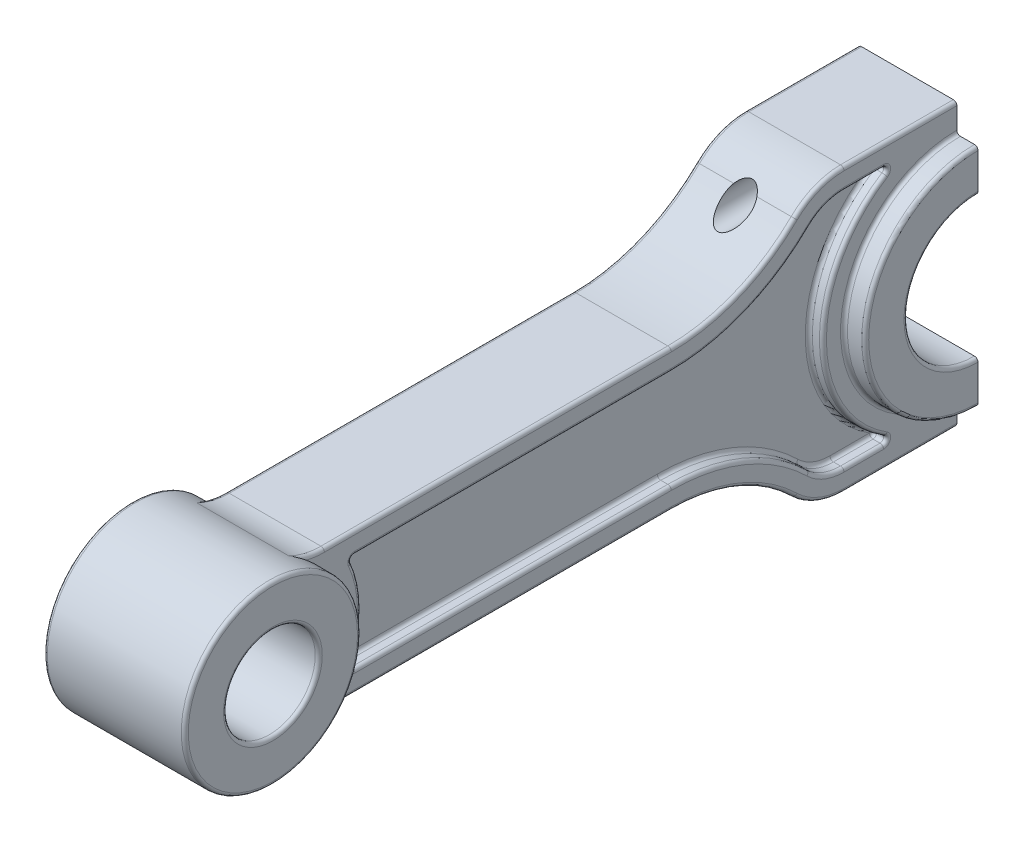
SolidWorks part; units mm, degrees
material "AISI 4340 Steel, normalized"
ref_plane "Front Plane" through (0, 0, 0) normal (1, 0, 0) x (0, 1, 0)
ref_plane "Top Plane" through (0, 0, 0) normal (0, 0, 1) x (0, 1, 0)
ref_plane "Right Plane" through (0, 0, 0) normal (0, 1, 0) x (-1, 0, 0)
sketch "Sketch1" plane through (0, 0, 0) normal (1, 0, 0) x (0, 1, 0)
  line L0 (-21.64, 0) -> (23.8326, 0) construction
  line L1 (-20, 16) -> (-20, 0)
  line L2 (0, 100) -> (0, -41.6338) construction
  line L3 (-10, 40.4949) -> (-10, 92.5)
  line L4 (-20, 0) -> (-10, 0)
  line L5 (10, 0) -> (20, 0)
  line L6 (-17, 16) -> (-17, 10.3923)
  line L7 (-7, 40.4949) -> (-7, 85.3798)
  line L8 (0, 19) -> (-26.4574, 19) construction
  line L9 (-17, 16) -> (-17, 0) construction
  line L10 (-7, 40.4949) -> (-7, 92.5) construction
  line L11 (17, 16) -> (17, 10.3923)
  line L12 (7, 40.4949) -> (7, 85.3798)
  line L13 (20, 16) -> (20, 0)
  line L14 (10, 40.4949) -> (10, 92.5)
  arc A0 (10, 0) -> (-10, 0) centre (0, 0) ccw
  arc A1 (16, 0) -> (-16, 0) centre (0, 0) ccw
  arc A2 (16.0769, 10.1258) -> (-16.0769, 10.1258) centre (0, 0) ccw
  arc A3 (-20, 16) -> (-17.1429, 22.9985) centre (-10, 16) cw
  arc A4 (-17.1429, 22.9985) -> (-10, 40.4949) centre (-35, 40.4949) ccw
  circle A5 centre (0, 100) radius 12.5
  circle A6 centre (0, 100) radius 6.5
  arc A7 (-11.1111, 94.2735) -> (-10, 89.6922) centre (-20, 89.6922) cw
  arc A8 (-17, 16) -> (-15, 20.899) centre (-10, 16) cw
  circle A9 centre (0, 0) radius 19 construction
  circle A10 centre (0, 0) radius 16 construction
  circle A11 centre (0, 0) radius 10 construction
  arc A12 (-15, 20.899) -> (-7, 40.4949) centre (-35, 40.4949) ccw
  arc A13 (-6.2969, 85.8367) -> (6.2969, 85.8367) centre (0, 100) ccw
  arc A14 (17, 16) -> (15, 20.899) centre (10, 16) ccw
  circle A15 centre (0, 100) radius 15.5 construction
  arc A16 (15, 20.899) -> (7, 40.4949) centre (35, 40.4949) cw
  arc A17 (20, 16) -> (17.1429, 22.9985) centre (10, 16) ccw
  arc A18 (17.1429, 22.9985) -> (10, 40.4949) centre (35, 40.4949) cw
  arc A19 (11.1111, 94.2735) -> (10, 89.6922) centre (20, 89.6922) ccw
  arc A20 (7, 85.3798) -> (6.2969, 85.8367) centre (6.5, 85.3798) ccw
  arc A21 (-7, 85.3798) -> (-6.2969, 85.8367) centre (-6.5, 85.3798) cw
  arc A22 (17, 10.3923) -> (16.0769, 10.1258) centre (16.5, 10.3923) cw
  arc A23 (-16.0769, 10.1258) -> (-17, 10.3923) centre (-16.5, 10.3923) cw
  point P9 (-16, 0)
  point P21 (19, 0)
  point P26 (15.5, 95)
  point P27 (16, 0)
  point P29 (9.563, 2.9237)
  point P64 (7, 86.1707)
  point P67 (-7, 86.1707)
  point P70 (17, 8.4853)
  point P73 (-17, 8.4853)
  dimension "D1" = 20
  dimension "D6" = 10
  dimension "D7" = 25
  dimension "D10" = 13
  dimension "D11" = 25
  dimension "D12" = 10
  dimension "D14" = 0.5
  dimension "D3" = 4
  dimension "D5" = 16
  dimension "D8" = 10
  dimension "D9" = 100
  dimension "D2" = 6
  dimension "D4" = 3
  dimension "D13" = 3
extrude "Boss-Extrude1" add sketch "Sketch1" along normal mid plane 20 contours L5 A1 L4 A0 region at (0, 0, 15.6422)
extrude "Boss-Extrude2" add sketch "Sketch1<3>" along normal mid plane 14 contours A17 A18 L14 A5 L3 A4 A3 L1 L4 A1 L5 L13 A16 A14 L11 A2 L6 A8 A12 L7 A13 L12 | A5 A7 L3 | A19 A5 L14 region at (0, -18.3252, 19.3987) region at (0, -10.2405, 92.2447) region at (0, 10.2405, 92.2447)
sketch "Sketch1<3>" plane through (0, 0, 0) normal (1, 0, 0) x (0, 1, 0) same geometry as "Sketch1"
extrude "Boss-Extrude3" add sketch "Sketch1<4>" along normal mid plane 20 contours A5 A6 region at (0, -10.2931, 93.5511)
sketch "Sketch1<4>" plane through (0, 0, 0) normal (1, 0, 0) x (0, 1, 0) same geometry as "Sketch1"
extrude "Boss-Extrude4" add sketch "Sketch1<6>" along normal mid plane 10 contours A14 A16 L12 A13 L7 A12 A8 L6 A2 L11 region at (0, 0, 45.7737)
sketch "Sketch1<6>" plane through (0, 0, 0) normal (1, 0, 0) x (0, 1, 0) same geometry as "Sketch1"
fillet "Fillet1" radius 0.5 60 edges at (-5, -17, 13.1962) (-5, -16.4807, 18.6458) (-5, -7, 62.9374) (-5, 17, 13.1962) (-5, 16.4807, 18.6458) (-5, 7, 62.9374) (-7, 17, 13.1962) (-7, 16.4807, 18.6458) (-7, 7, 62.9374) (-7, -7, 62.9374) (-7, -9.077, 29.9119) (-7, -16.4807, 18.6458) (7, -17, 13.1962) (7, -16.4807, 18.6458) (7, -9.077, 29.9119) (5, -17, 13.1962) (5, -16.4807, 18.6458) (5, -9.077, 29.9119) (7, 17, 13.1962) (7, 16.4807, 18.6458) (7, 7, 62.9374) (5, 17, 13.1962) (5, 16.4807, 18.6458) (5, 7, 62.9374) (-5, 0, 84.5) (-5, -9.077, 29.9119) (-5, 9.077, 29.9119) (-7, 9.077, 29.9119) (-7, -17, 13.1962) (-5, 0, 19) (-7, 0, 19) (-7, 0, 16) (-10, 0, 16) (-7, 0, 84.5) (7, 0, 84.5) (7, -7, 62.9374) (5, -7, 62.9374) (7, 9.077, 29.9119) (5, 9.077, 29.9119) (5, 0, 19) (7, 0, 19) (7, 0, 16) (10, 0, 16) (5, 0, 84.5) (-5, 16.6387, 9.9119) (-5, 6.7724, 85.7991) (-5, -6.7724, 85.7991) (-5, -16.6387, 9.9119) (-7, -6.7724, 85.7991) (-7, -16.6387, 9.9119) (-7, 16.6387, 9.9119) (-7, 6.7724, 85.7991) (5, 16.6387, 9.9119) (5, 6.7724, 85.7991) (5, -6.7724, 85.7991) (5, -16.6387, 9.9119) (7, 16.6387, 9.9119) (7, 6.7724, 85.7991) (7, -6.7724, 85.7991) (7, -16.6387, 9.9119)
fillet "Fillet2" radius 0.5 24 edges at (-7, 20, 8) (-7, 19.2582, 19.7796) (-7, 11.8545, 31.0458) (-7, 10.2817, 92.0493) (7, 20, 8) (7, 19.2582, 19.7796) (7, 11.8545, 31.0458) (7, 10.2817, 92.0493) (7, -20, 8) (7, -19.2582, 19.7796) (7, -11.8545, 31.0458) (7, -10.2817, 92.0493) (-7, -20, 8) (-7, -19.2582, 19.7796) (-7, -11.8545, 31.0458) (-7, -10.2817, 92.0493) (-7, 10, 65.0936) (7, 10, 65.0936) (7, -10, 65.0936) (-7, -10, 65.0936) (-10, 0, 87.5) (-10, 0, 93.5) (10, 0, 93.5) (10, 0, 87.5)
sketch "Sketch4" plane through (0, 0, 0) normal (0, 0, -1) x (1, 0, 0)
  line L0 (-2.306, 0) -> (2.6729, 0) construction
  circle A0 centre (0, 16) radius 2
  circle A2 centre (0, -16) radius 2
  dimension "D1" = 32
  dimension "D2" = 4
extrude "Cut-Extrude1" cut sketch "Sketch4" against normal blind 36
ref_axis "Axis1" through (9.5, 0, 100) along (-1, 0, 0)
fillet "Fillet3" radius 0.5 2 edges at (-10, 0, 10) (10, 0, 10)
